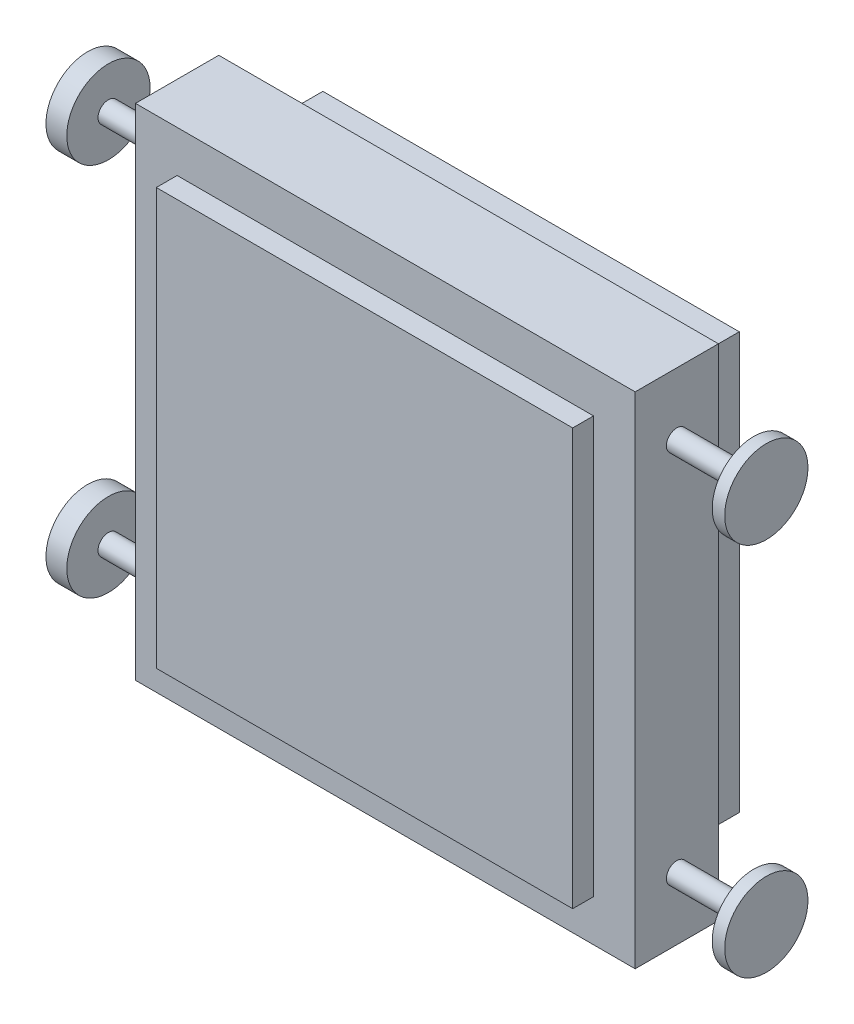
SolidWorks part; units mm, degrees
ref_plane "Спереди" through (0, 0, 0) normal (0, 0, 1) x (1, 0, 0)
ref_plane "Сверху" through (0, 0, 0) normal (0, 1, 0) x (1, 0, 0)
ref_plane "Справа" through (0, 0, 0) normal (1, 0, 0) x (0, 0, -1)
sketch "Эскиз1" plane through (0, 0, 0) normal (0, 0, 1) x (1, 0, 0)
  line L1 (-400, 400) -> (400, 400)
  line L2 (-400, 400) -> (-400, -400)
  line L3 (-400, -400) -> (400, -400)
  line L4 (400, 400) -> (400, -400)
  point P4 (0, 400)
  point P6 (400, 0)
  dimension "D1" = 800
  dimension "D2" = 800
extrude "Бобышка-Вытянуть1" add sketch "Эскиз1" along normal blind 100
sketch "Эскиз2" plane through (0, 0, 0) normal (0, 0, 1) x (1, 0, 0)
  line L0 (400, 400) -> (-400, 400) construction
  line L1 (-500, 500) -> (500, 500)
  line L2 (-500, 500) -> (-500, -500)
  line L3 (-500, -500) -> (500, -500)
  line L4 (500, 500) -> (500, -500)
  line L5 (-400, -400) -> (400, -400) construction
  line L6 (400, -400) -> (400, 400) construction
  line L7 (-400, 400) -> (-400, -400) construction
  line L9 (-600, 600) -> (600, 600)
  line L10 (-600, 600) -> (-600, -600)
  line L11 (-600, -600) -> (600, -600)
  line L12 (600, 600) -> (600, -600)
  dimension "D1" = 100
  dimension "D2" = 100
  dimension "D3" = 100
  dimension "D4" = 100
  dimension "D5" = 100
  dimension "D6" = 100
  dimension "D7" = 100
  dimension "D8" = 100
extrude "Бобышка-Вытянуть2" add sketch "Эскиз2" along normal blind 400 from offset 25 separate body contours L4 L1 L2 L3 region at (0, 0, 0)
extrude "Бобышка-Вытянуть3" add sketch "Эскиз2<3>" along normal blind 200 from offset 175 separate body
sketch "Эскиз2<3>" plane through (0, 0, 0) normal (0, 0, 1) x (1, 0, 0) same geometry as "Эскиз2"
sketch "Эскиз4" plane through (0, 0, 0) normal (1, 0, 0) x (0, 0, -1)
  line L0 (-375, -600) -> (-175, -600) construction
  line L1 (-375, 600) -> (-175, 600) construction
  circle A0 centre (-275, -450) radius 100
  circle A1 centre (-275, 450) radius 100
  circle A2 centre (-275, 450) radius 25
  circle A3 centre (-275, -450) radius 25
  point P8 (-275, -600)
  point P11 (-275, 600)
  dimension "D1" = 200
  dimension "D2" = 50
  dimension "D3" = 150
  dimension "D4" = 150
extrude "Бобышка-Вытянуть4" add sketch "Эскиз4" along normal mid plane 1630 contours A2 | A3 region at (0, 450, 275) region at (0, -450, 275)
extrude "Бобышка-Вытянуть5" add sketch "Эскиз4<3>" against normal blind 30 from surface starting at face at (815, 450, 250)
sketch "Эскиз4<3>" plane through (0, 0, 0) normal (1, 0, 0) x (0, 0, -1) same geometry as "Эскиз4"
extrude "Бобышка-Вытянуть6" add sketch "Эскиз4<4>" along normal blind 50 from surface starting at face at (-815, 450, 250)
sketch "Эскиз4<4>" plane through (0, 0, 0) normal (1, 0, 0) x (0, 0, -1) same geometry as "Эскиз4"
